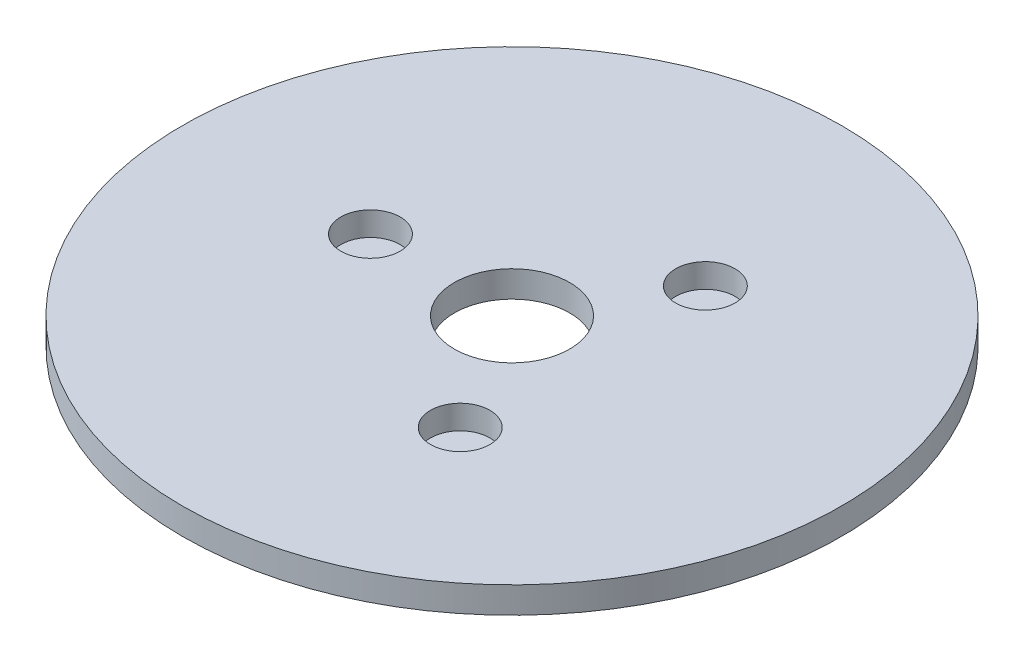
SolidWorks part; units mm, degrees
ref_plane "Front Plane" through (0, 0, 0) normal (0, 0, 1) x (1, 0, 0)
ref_plane "Top Plane" through (0, 0, 0) normal (0, 1, 0) x (1, 0, 0)
ref_plane "Right Plane" through (0, 0, 0) normal (1, 0, 0) x (0, 0, -1)
sketch "Sketch1" plane through (0, 0, 0) normal (0, 1, 0) x (1, 0, 0)
  circle A0 centre (0, 0) radius 100
  dimension "FLANGE_OD" = 200
extrude "Boss-Extrude1" add sketch "Sketch1" along normal blind 8
sketch "Sketch2" plane through (0, 0, 0) normal (0, 1, 0) x (1, 0, 0)
  circle A0 centre (0, 0) radius 17.5
  dimension "BORE_D" = 35
extrude "Cut-Extrude1" cut sketch "Sketch2" along normal through all
sketch "Sketch3" plane through (0, 8, 0) normal (0, 1, 0) x (1, 0, 0)
  circle A0 centre (0, 0) radius 42.948 construction
  circle A1 centre (-42.948, 0) radius 9.0099
  dimension "BOLT_D" = 18.0198
  dimension "BOLT_PCD" = 85.896
extrude "Cut-Extrude2" cut sketch "Sketch3" against normal blind 7.2693
pattern_circular "CirPattern1" count 3 over 360 about axis through (0, 0, 0) along (0, 1, 0) of "Cut-Extrude2"
